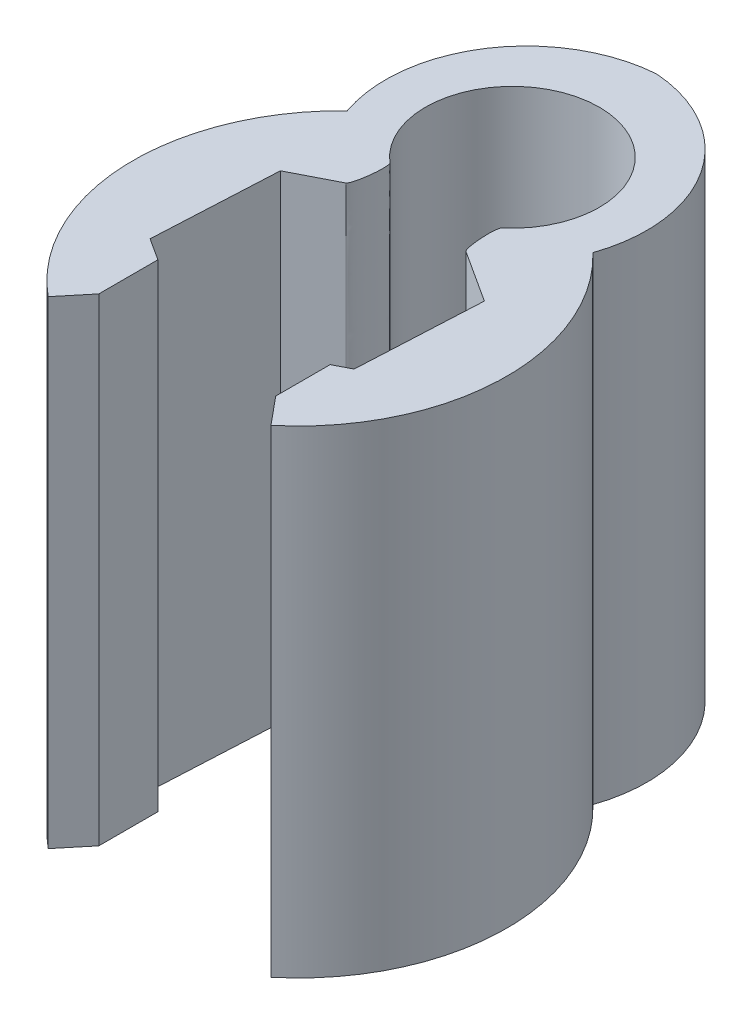
SolidWorks part; units mm, degrees
ref_plane "Front Plane" through (0, 0, 0) normal (0, 0, 1) x (1, 0, 0)
ref_plane "Top Plane" through (0, 0, 0) normal (0, 1, 0) x (1, 0, 0)
ref_plane "Right Plane" through (0, 0, 0) normal (1, 0, 0) x (0, 0, -1)
sketch "Sketch3" plane through (0, 0, 0) normal (0, 1, 0) x (1, 0, 0)
  line L0 (-7.2765, 0.1114) -> (11.8281, 0.1114) construction
  line L1 (-2.4796, 5.151) -> (-2.4796, 6.4742)
  line L2 (5.874, 3.0075) -> (0.3324, 6.5907)
  line L3 (0.3324, 6.5907) -> (-5.5415, 3.5833)
  line L4 (-5.5415, 3.5833) -> (-5.874, -3.0075)
  line L5 (-5.874, -3.0075) -> (-0.3324, -6.5907)
  line L6 (-0.3324, -6.5907) -> (5.5415, -3.5833)
  line L7 (5.5415, -3.5833) -> (5.874, 3.0075)
  line L8 (2.4796, 5.151) -> (2.4796, 6.4742)
  line L9 (-4.7012, -3.7658) -> (-4.7012, -6.9056)
  line L10 (-4.7012, -6.9056) -> (-5.9188, -8.3785)
  line L11 (0, 2.9063) -> (0, -1.8101) construction
  line L12 (4.7012, -6.9056) -> (5.9188, -8.3785)
  line L13 (4.7012, -3.7658) -> (4.7012, -6.9056)
  circle A0 centre (0, 0) radius 5.715 construction
  circle A1 centre (0, 10.3692) radius 4.6174
  arc A2 (-5.9188, -8.3785) -> (-6.5266, 8.121) centre (1.1246, 0.1419) cw
  arc A3 (-6.5266, 8.121) -> (0, 18.035) centre (0.5425, 10.5725) cw
  arc A4 (6.5266, 8.121) -> (0, 18.035) centre (-0.5425, 10.5725) ccw
  arc A5 (5.9188, -8.3785) -> (6.5266, 8.121) centre (-1.1246, 0.1419) ccw
  dimension "D1" = 11.43
  dimension "D2" = 0
extrude "Boss-Extrude1" add sketch "Sketch3" along normal blind 25.4 contours L12 A5 A4 A3 A2 L10 L9 L5 L4 L3 L1 A1 L8 L2 L7 L6 L13 | A1 L1 L3 | A1 L2 L8 region at (-4.1612, 0, -4.6613) region at (-2.0247, 0, -5.8096) region at (2.1055, 0, -5.8575)
fillet "Fillet6" radius 1.27 2 edges at (1.328, 12.7, -5.947) (-1.0635, 12.7, -5.876) conic radius 6.35
sketch "Sketch4" plane through (0, 25.4, 0) normal (0, 1, 0) x (1, 0, 0)
  line L1 (-6.1573, 3.9814) -> (-6.5266, -3.3416)
  line L2 (-6.5266, -3.3416) -> (-0.3694, -7.323)
  line L3 (-0.3694, -7.323) -> (6.1573, -3.9814)
  line L4 (6.1573, -3.9814) -> (6.5266, 3.3416)
  line L5 (6.5266, 3.3416) -> (0.3694, 7.323)
  line L6 (0.3694, 7.323) -> (-6.1573, 3.9814)
  circle A0 centre (0, 0) radius 6.35 construction
